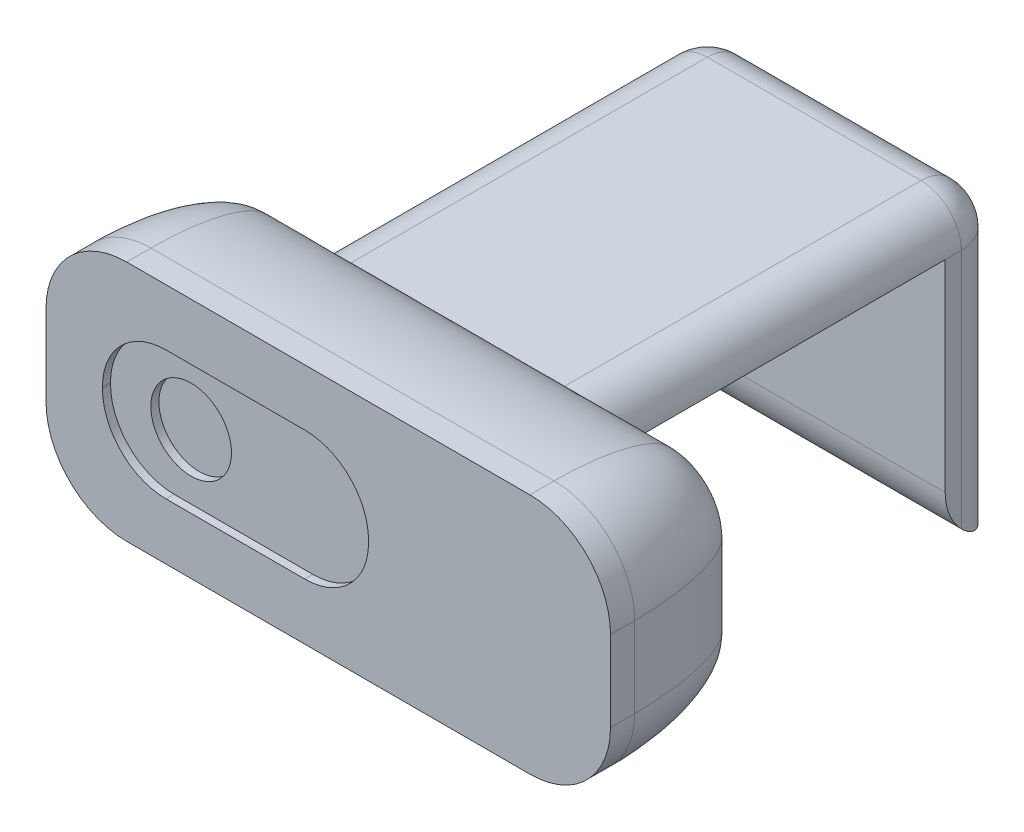
SolidWorks part; units mm, degrees
material "ABS"
ref_plane "Plano frontal" through (0, 0, 0) normal (0, 0, 1) x (1, 0, 0)
ref_plane "Plano superior" through (0, 0, 0) normal (0, 1, 0) x (1, 0, 0)
ref_plane "Plano direito" through (0, 0, 0) normal (1, 0, 0) x (0, 0, -1)
sketch "Esboço1" plane through (0, 0, 0) normal (0, 0, 1) x (1, 0, 0)
  line L0 (-35, 0) -> (-28, 0) construction
  line L1 (-25, -15) -> (25, -15)
  line L2 (-35, -5) -> (-35, 5)
  line L3 (-25, 15) -> (25, 15)
  line L4 (35, -5) -> (35, 5)
  line L5 (-35, -15) -> (35, 15) construction
  line L6 (-35, 15) -> (35, -15) construction
  line L7 (-28, 0) -> (-18, 0) construction
  line L8 (-18, 0) -> (5, 0) construction
  line L9 (5, 0) -> (35, 0) construction
  arc A0 (25, 15) -> (35, 5) centre (25, 5) cw
  arc A1 (25, -15) -> (35, -5) centre (25, -5) ccw
  arc A2 (-25, -15) -> (-35, -5) centre (-25, -5) cw
  arc A3 (-35, 5) -> (-25, 15) centre (-25, 5) cw
  point P0 (0, 0)
  dimension "D3" = 10
  dimension "D1" = 70
  dimension "D2" = 30
  dimension "D4" = 7
  dimension "D5" = 10
  dimension "D6" = 30
extrude "Ressalto-extrusão1" add sketch "Esboço1" along normal blind 18
fillet "Filete1" radius 5 8 edges at (0, -15, 0) (32.0711, -12.0711, 0) (-32.0711, -12.0711, 0) (35, 0, 0) (-35, 0, 0) (32.0711, 12.0711, 0) (-32.0711, 12.0711, 0) (0, 15, 0) second distance 15 first distance on face at (0, 0, 0)
sketch "Esboço2" plane through (0, 0, 18) normal (0, 0, 1) x (1, 0, 0)
  line L0 (-35, 0) -> (-28, 0) construction
  line L1 (-35, 5) -> (-35, -5) construction
  line L2 (-28, 0) -> (-18, 0) construction
  line L3 (-18, 0) -> (5, 0) construction
  line L4 (5, 0) -> (35, 0) construction
  line L5 (35, -5) -> (35, 5) construction
  circle A0 centre (-18, 0) radius 5
  dimension "D4" = 10
  dimension "D1" = 7
  dimension "D2" = 10
  dimension "D3" = 30
extrude "Corte-extrusão1" cut sketch "Esboço2" against normal blind 2
sketch "Esboço3" plane through (0, 0, 18) normal (0, 0, 1) x (1, 0, 0)
  line L0 (-35, 0) -> (-28, 0) construction
  line L1 (-35, 5) -> (-35, -5) construction
  line L2 (-28, 0) -> (5, 0) construction
  line L3 (5, 0) -> (35, 0) construction
  line L4 (35, -5) -> (35, 5) construction
  line L5 (-11.5, 15) -> (-11.5, 8) construction
  line L6 (25, 15) -> (-25, 15) construction
  line L7 (-11.5, 8) -> (-11.5, -8) construction
  line L8 (-11.5, -8) -> (-11.5, -15) construction
  line L9 (-25, -15) -> (25, -15) construction
  line L11 (-2.9, -8) -> (-20.1, -8)
  line L12 (5, -0.1) -> (5, 0.1)
  line L13 (-2.9, 8) -> (-20.1, 8)
  line L14 (-28, -0.1) -> (-28, 0.1)
  line L15 (5, -8) -> (-28, 8) construction
  line L16 (5, 8) -> (-28, -8) construction
  arc A0 (-20.1, -8) -> (-28, -0.1) centre (-20.1, -0.1) cw
  arc A1 (-2.9, -8) -> (5, -0.1) centre (-2.9, -0.1) ccw
  arc A2 (5, 0.1) -> (-2.9, 8) centre (-2.9, 0.1) ccw
  arc A3 (-20.1, 8) -> (-28, 0.1) centre (-20.1, 0.1) ccw
  point P17 (-11.5, 0)
  point P18 (-11.5, 0)
  dimension "D4" = 7.9
  dimension "D1" = 30
  dimension "D2" = 7
  dimension "D3" = 16
extrude "Corte-extrusão2" cut sketch "Esboço3" against normal blind 1
sketch "Esboço4" plane through (0, 0, 0) normal (0, 0, -1) x (-1, 0, 0)
  line L0 (30, 0) -> (26, 0) construction
  line L1 (30, -5) -> (30, 5) construction
  line L2 (26, 0) -> (-10.5, 0) construction
  line L3 (-10.5, 0) -> (-30, 0) construction
  line L4 (-30, 5) -> (-30, -5) construction
  line L6 (-10.5, 0) -> (26, 0)
  line L7 (-10.5, 0) -> (-10.5, 5)
  line L8 (-10.5, 5) -> (26, 5)
  line L9 (26, 0) -> (26, 5)
  dimension "D1" = 4
  dimension "D2" = 36.5
  dimension "D3" = 5
extrude "Ressalto-extrusão2" add sketch "Esboço4" along normal blind 55
fillet "Filete2" radius 5 2 edges at (-26, 5, -27.5) (10.5, 5, -27.5)
sketch "Esboço5" plane through (0, 0, 0) normal (0, -1, 0) x (1, 0, 0)
  line L0 (10.5, -55) -> (10.5, 0) construction
  line L1 (-26, -55) -> (10.5, -55)
  line L2 (-26, -55) -> (-26, -48)
  line L3 (-26, -48) -> (10.5, -48)
  line L4 (10.5, -55) -> (10.5, -48)
  dimension "D1" = 7
extrude "Ressalto-extrusão3" add sketch "Esboço5" along normal blind 32
fillet "Filete3" radius 5 5 edges at (-26, -16, -55) (-24.5355, 3.5355, -55) (-7.75, 5, -55) (9.0355, 3.5355, -55) (10.5, -16, -55)
fillet "Filete4" radius 7 1 edges at (-7.75, -32, -48)
